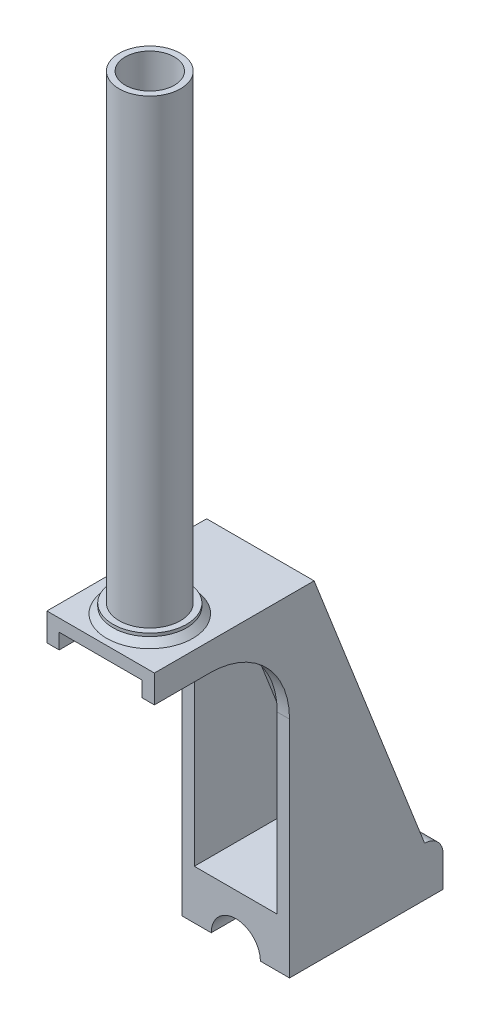
SolidWorks part; units mm, degrees
material "AISI 1020"
ref_plane "Front Plane" through (0, 0, 0) normal (0, 0, 1) x (1, 0, 0)
ref_plane "Top Plane" through (0, 0, 0) normal (0, 1, 0) x (1, 0, 0)
ref_plane "Right Plane" through (0, 0, 0) normal (1, 0, 0) x (0, 0, -1)
sketch "Sketch1" plane through (0, 0, 0) normal (1, 0, 0) x (0, 0, -1)
  line L0 (8, 157) -> (8, 0)
  line L1 (8, 0) -> (10, 0)
  line L2 (12, 4) -> (12, 7)
  line L3 (12, 7) -> (10, 7)
  line L4 (10, 7) -> (10, 157)
  line L5 (10, 157) -> (8, 157)
  line L6 (0, 0) -> (0, 135.9935) construction
  line L7 (10, 0) -> (10, 4)
  line L8 (10, 4) -> (12, 4)
  dimension "D1" = 150
  dimension "D2" = 4
  dimension "D3" = 16
  dimension "D4" = 20
  dimension "D5" = 2
  dimension "D6" = 3
revolve "Revolve1" add sketch "Sketch1" angle 360 about L6
sketch "Sketch2" plane through (0, 0, 0) normal (1, 0, 0) x (0, 0, -1)
  line L0 (28, -88) -> (78, -88)
  line L1 (28, -88) -> (28, -104)
  line L2 (78, -88) -> (78, -104)
  line L3 (28, -104) -> (78, -104)
  dimension "D1" = 50
  dimension "D2" = 28
  dimension "D3" = 16
  dimension "D4" = 88
extrude "Boss-Extrude1" add sketch "Sketch2" along normal mid plane 35
ref_plane "Plane1" through (0, 0, -78) normal (0, 0, -1) x (-1, 0, 0)
sketch "Sketch3" plane through (0, 0, -78) normal (0, 0, -1) x (-1, 0, 0)
  line L1 (-17.5, -104) -> (17.5, -104) construction
  circle A0 centre (0, -104) radius 8
  dimension "D1" = 16
extrude "Cut-Extrude1" cut sketch "Sketch3" against normal through all
sketch "Sketch4" plane through (0, 0, -78) normal (0, 0, -1) x (-1, 0, 0)
  line L0 (0, -99) -> (0, 0) construction
  line L1 (8, -96) -> (-8, -96)
  line L2 (8, -96) -> (8, -99)
  line L3 (8, -99) -> (-8, -99)
  line L4 (-8, -96) -> (-8, -99)
  arc A1 (8, -104) -> (-8, -104) centre (0, -104) ccw construction
  point P9 (0, -96)
  dimension "D1" = 3
  dimension "D2" = 16
extrude "Boss-Extrude2" add sketch "Sketch4" against normal blind 43 from offset 3 offset against normal yes
fillet "Fillet1" radius 0.5 2 edges at (0, -99, -75) (0, -99, -32)
fillet "Fillet2" radius 6 1 edges at (0, -88, -78)
sketch "Sketch6" plane through (0, -104, 0) normal (0, -1, 0) x (1, 0, 0)
  circle A0 centre (-12.5, -34) radius 3 construction
  circle A1 centre (12.5, -34) radius 3 construction
  circle A2 centre (-12.5, -72) radius 3 construction
  circle A3 centre (12.5, -72) radius 3 construction
  circle A4 centre (-12.5, -34) radius 3
  circle A5 centre (12.5, -34) radius 3
  circle A6 centre (-12.5, -72) radius 3
  circle A7 centre (12.5, -72) radius 3
extrude "Cut-Extrude3" cut sketch "Sketch6" against normal blind 12
sketch "Sketch7" plane through (-17.5, 0, 0) normal (-1, 0, 0) x (0, 0, 1)
  line L0 (-72, -88) -> (-36, 4)
  line L1 (-36, 4) -> (16, 4)
  line L2 (16, 4) -> (16, -5)
  line L3 (16, -5) -> (-2, -5)
  line L4 (-28, -31) -> (-28, -88)
  line L5 (-72, -88) -> (-28, -88) construction
  line L6 (-12, 4) -> (12, 4) construction
  line L7 (-72, -88) -> (-28, -88)
  arc A0 (-2, -5) -> (-28, -31) centre (-2, -31) ccw
  dimension "D3" = 26
  dimension "D1" = 83
  dimension "D2" = 16
  dimension "D4" = 36
extrude "Boss-Extrude3" add sketch "Sketch7" against normal blind 4 separate body
extrude "Boss-Extrude5" add sketch "Sketch7<2>" along normal blind 4 from offset 35 separate body offset against normal yes
sketch "Sketch7<2>" plane through (-17.5, 0, 0) normal (-1, 0, 0) x (0, 0, 1) same geometry as "Sketch7"
sketch "Sketch8" plane through (0, 4, 0) normal (0, -1, 0) x (1, 0, 0)
  line L0 (-13.5, 16) -> (13.5, 16)
  line L1 (13.5, 16) -> (13.5, -36)
  line L2 (13.5, -36) -> (-13.5, -36)
  line L3 (-13.5, -36) -> (-13.5, 16)
  circle A0 centre (0, 0) radius 10 construction
  circle A1 centre (0, 0) radius 10
extrude "Boss-Extrude6" add sketch "Sketch8" along normal blind 4
chamfer "Chamfer1" distance 4 distance2 3 1 edges at (0, 0, -36) first distance on face at (0, 2, -36)
sketch "Sketch9" plane through (0, 12.7475, -32.577) normal (0, 0.3644, -0.9312) x (-1, 0, 0)
  line L1 (-13.5, -9.3934) -> (13.5, -9.3934)
  line L2 (-13.5, -9.3934) -> (-13.5, -108.1861)
  line L3 (-13.5, -108.1861) -> (13.5, -108.1861)
  line L4 (13.5, -9.3934) -> (13.5, -108.1861)
extrude "Boss-Extrude7" add sketch "Sketch9" against normal blind 4
chamfer "Chamfer2" distance 2 angle 45 1 edges at (0, 4, -12)
